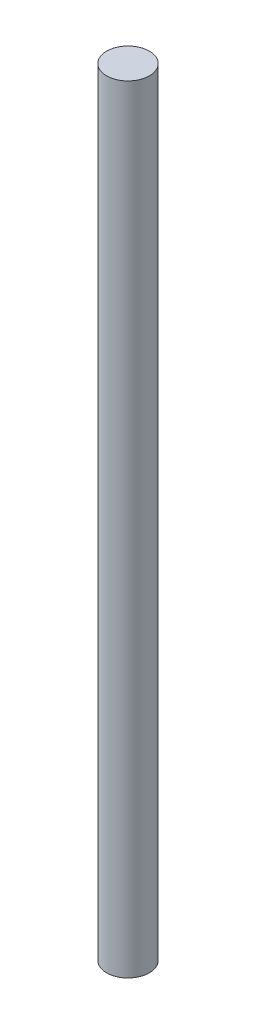
SolidWorks part; units mm, degrees
ref_plane "前视基准面" through (0, 0, 0) normal (0, 0, 1) x (1, 0, 0)
ref_plane "上视基准面" through (0, 0, 0) normal (0, 1, 0) x (1, 0, 0)
ref_plane "右视基准面" through (0, 0, 0) normal (1, 0, 0) x (0, 0, -1)
sketch "草图1" plane through (0, 0, 0) normal (0, 1, 0) x (1, 0, 0)
  circle A0 centre (0, 0) radius 1
  dimension "D1" = 2
extrude "凸台-拉伸1" add sketch "草图1" along normal blind 36.3
